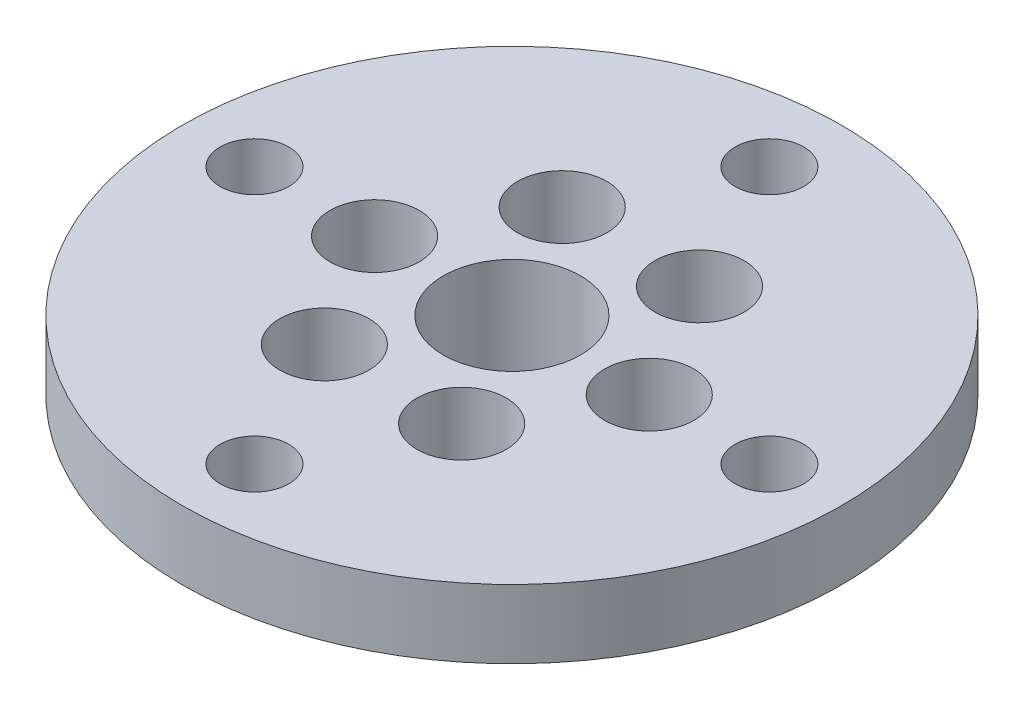
SolidWorks part; units mm, degrees
ref_plane "Front Plane" through (0, 0, 0) normal (0, 0, 1) x (1, 0, 0)
ref_plane "Top Plane" through (0, 0, 0) normal (0, 1, 0) x (1, 0, 0)
ref_plane "Right Plane" through (0, 0, 0) normal (1, 0, 0) x (0, 0, -1)
sketch "Sketch1" plane through (0, 0, 0) normal (0, 1, 0) x (1, 0, 0)
  circle A0 centre (0, 0) radius 15
  dimension "D1" = 30
extrude "Boss-Extrude1" add sketch "Sketch1" along normal blind 5
sketch "Sketch2" plane through (0, 0, 0) normal (0, 1, 0) x (1, 0, 0)
  circle A0 centre (0, 0) radius 13.5 construction
  circle A1 centre (-5, 8.6603) radius 1.25
  circle A2 centre (5, 8.6603) radius 1.25
  circle A3 centre (10, 0) radius 1.25
  circle A4 centre (5, -8.6603) radius 1.25
  circle A5 centre (-5, -8.6603) radius 1.25
  circle A6 centre (-10, 0) radius 1.25
  circle A7 centre (0, 0) radius 10 construction
  circle A8 centre (0, 0) radius 5
  point P3 (-10, 0)
  point P4 (-5, 8.6603)
  point P5 (5, 8.6603)
  point P6 (10, 0)
  point P7 (5, -8.6603)
  point P8 (-5, -8.6603)
  point P23 (0, 0)
  dimension "D1" = 27
  dimension "D2" = 2.5
  dimension "D4" = 20
  dimension "D5" = 10
  dimension "D3" = 6
sketch "Sketch3" plane through (0, 5, 0) normal (0, 1, 0) x (1, 0, 0)
  circle A0 centre (0, 0) radius 24
  dimension "D1" = 48
extrude "Boss-Extrude3" add sketch "Sketch3" along normal blind 5
extrude "Cut-Extrude1" cut sketch "Sketch2" along normal blind 11.5
sketch "Sketch4" plane through (0, 10, 0) normal (0, 1, 0) x (1, 0, 0)
  circle A1 centre (10, 0) radius 3.25
  circle A2 centre (5, 8.6603) radius 3.25
  circle A3 centre (5, 8.6603) radius 3.25
  circle A4 centre (5, -8.6603) radius 3.25
  circle A5 centre (-5, -8.6603) radius 3.25
  circle A6 centre (-10, 0) radius 3.25
  circle A7 centre (-5, 8.6603) radius 3.25
  point P15 (0, 0)
  dimension "D1" = 2
  dimension "D2" = 6
extrude "Cut-Extrude2" cut sketch "Sketch4" against normal offset from surface (6 mm away) 4 up to face at (5, 0, 9.9103)
sketch "Sketch5" plane through (0, 10, 0) normal (0, 1, 0) x (1, 0, 0)
  line L0 (0, 0) -> (0, 18.75) construction
  circle A0 centre (0, 0) radius 18.75 construction
  circle A1 centre (0, 18.75) radius 2.5
  circle A2 centre (18.75, 0) radius 2.5
  circle A3 centre (0, -18.75) radius 2.5
  circle A4 centre (-18.75, 0) radius 2.5
  point P14 (0, 0)
  dimension "D1" = 37.5
  dimension "D2" = 5
  dimension "D3" = 4
extrude "Cut-Extrude3" cut sketch "Sketch5" against normal offset from surface (6.5 mm away) 3.5 up to face at (5, 0, 9.9103)
